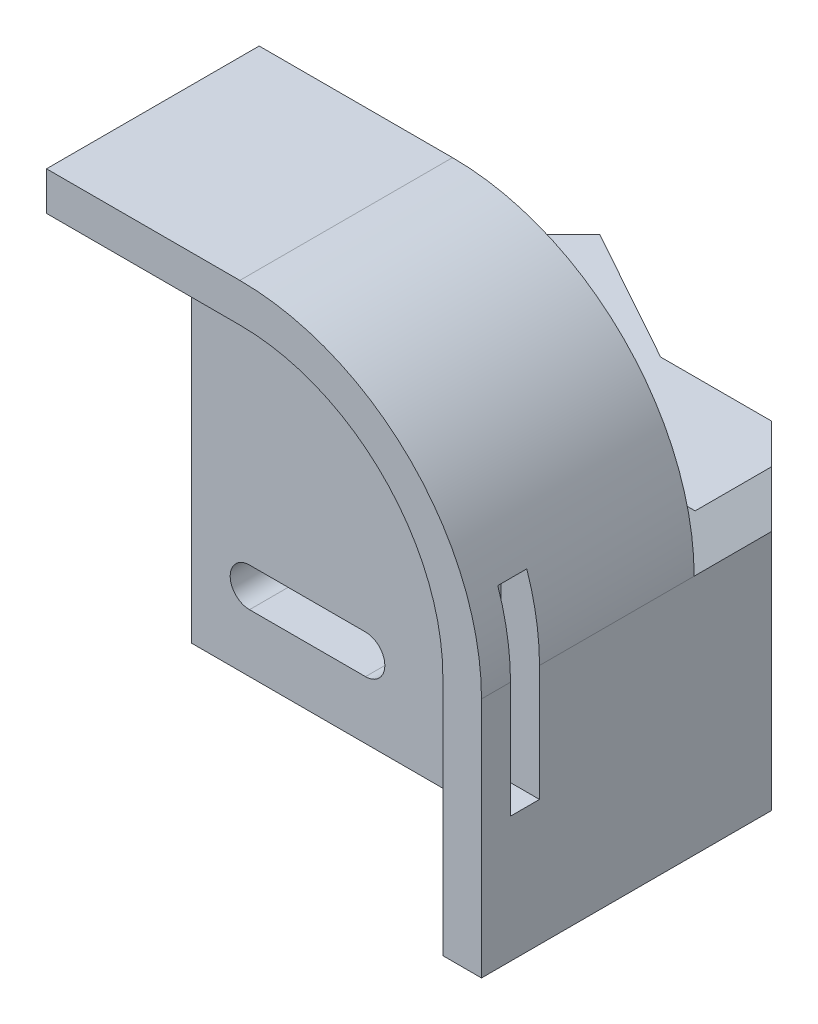
SolidWorks part; units mm, degrees
ref_plane "Front Plane" through (0, 0, 0) normal (0, 0, 1) x (1, 0, 0)
ref_plane "Top Plane" through (0, 0, 0) normal (0, 1, 0) x (1, 0, 0)
ref_plane "Right Plane" through (0, 0, 0) normal (1, 0, 0) x (0, 0, -1)
sketch "Sketch1" plane through (0, 0, 0) normal (0, 0, 1) x (1, 0, 0)
  line L0 (0, 25) -> (-20, 25)
  line L1 (-20, 25) -> (-20, -25)
  line L6 (-20, -25) -> (25, -25)
  line L7 (25, -25) -> (25, 0)
  arc A1 (25, 0) -> (0, 25) centre (0, 0) ccw
  dimension "D1" = 25
  dimension "D2" = 45
  dimension "D3" = 50
extrude "Boss-Extrude1" add sketch "Sketch1" along normal blind 7
sketch "Sketch3" plane through (0, 0, 7) normal (0, 0, 1) x (1, 0, 0)
  line L0 (25, -25) -> (25, 0) construction
  line L1 (0, 25) -> (-20, 25) construction
  line L2 (25, -25) -> (25, 0)
  line L3 (0, 25) -> (-20, 25)
  arc A0 (25, 0) -> (0, 25) centre (0, 0) ccw construction
  arc A1 (25, 0) -> (0, 25) centre (0, 0) ccw
extrude "Extrude-Thin2" add sketch "Sketch3" along normal blind 15 thin thin type one direction reverse wall 4
fillet "Fillet1" radius 7 3 edges at (-10, 21, 7) (14.8492, 14.8492, 7) (21, -12.5, 7)
sketch "Sketch5" plane through (25, 0, 0) normal (1, 0, 0) x (0, 0, -1)
  line L1 (0, -25) -> (15, -25)
  line L2 (0, -25) -> (0, 0)
  line L3 (0, 0) -> (15, 0)
  line L4 (15, -25) -> (15, 0)
  dimension "D1" = 15
extrude "Boss-Extrude2" add sketch "Sketch5" against normal blind 8
sketch "Sketch8" plane through (0, 0, 7) normal (0, 0, 1) x (1, 0, 0)
  line L0 (-20, -17) -> (-2, -17) construction
  line L1 (-20, 14) -> (-20, -25) construction
  line L2 (-20, -25) -> (14, -25) construction
  line L3 (-14, -15) -> (-2, -15)
  line L5 (-14, -19) -> (-2, -19)
  arc A0 (-2, -19) -> (-2, -15) centre (-2, -17) ccw
  arc A1 (-14, -15) -> (-14, -19) centre (-14, -17) ccw
  arc A2 (-2, -15) -> (-4, -17) centre (-2, -17) ccw construction
  arc A3 (-4, -17) -> (-2, -19) centre (-2, -17) ccw construction
  arc A4 (-12, -17) -> (-14, -15) centre (-14, -17) ccw construction
  arc A5 (-14, -19) -> (-12, -17) centre (-14, -17) ccw construction
  dimension "D1" = 4
  dimension "D2" = 12
  dimension "D3" = 6
  dimension "D4" = 8
extrude "Cut-Extrude2" cut sketch "Sketch8" against normal through all
pattern_linear "LPattern1" count 2 spacing 26 along (0, 1, 0) of "Cut-Extrude2"
chamfer "Chamfer3" distance 7 angle 45 1 edges at (25, -12.5, -15)
sketch "Sketch9" plane through (17, 0, 0) normal (-1, 0, 0) x (0, 0, 1)
  line L0 (0, 0) -> (0, -25) construction
  line L1 (-15, 0) -> (0, 0)
  line L2 (-15, 0) -> (-15, -7)
  line L3 (-15, -7) -> (0, -7)
  line L4 (0, 0) -> (0, -7)
  dimension "D1" = 7
extrude "Boss-Extrude3" add sketch "Sketch9" along normal blind 15
sketch "Sketch10" plane through (0, -7, 0) normal (0, -1, 0) x (1, 0, 0)
  line L0 (2, -15) -> (-6.9706, -15)
  line L1 (-6.9706, -15) -> (-12.6274, -9.3431)
  line L2 (-12.6274, -9.3431) -> (-16.8701, -13.5858)
  line L3 (-16.8701, -13.5858) -> (-20, -10.4558)
  line L4 (-6.9706, -7.9289) -> (-10.5061, -11.4645) construction
  line L5 (-20, -10.4558) -> (-20, 0)
  line L6 (-20, 0) -> (17, 0)
  line L7 (17, 0) -> (17, -15)
  line L8 (17, -15) -> (2, -15)
  line L9 (-4.8492, -10.0503) -> (-9.0919, -5.8076)
  line L10 (-9.0919, -5.8076) -> (-6.9706, -3.6863)
  line L11 (-6.9706, -3.6863) -> (-2.7279, -7.9289)
  line L12 (-2.7279, -7.9289) -> (-4.8492, -10.0503)
  line L14 (4.3431, -34.799) -> (-16.8701, -13.5858) construction
  dimension "D1" = 3
  dimension "D2" = 5
  dimension "D3" = 6
extrude "Boss-Extrude4" add sketch "Sketch10" against normal offset from surface 2 and the other way blind 2
sketch "Sketch13" plane through (-10.9853, 0, -10.9853) normal (-0.7071, 0, -0.7071) x (-0.7071, 0, 0.7071)
  line L0 (2.3223, -9) -> (2.3223, 2.9) construction
  line L1 (-5.6777, 2.9) -> (2.3223, 2.9)
  line L2 (-5.6777, 2.9) -> (-5.6777, 0.9)
  line L3 (-5.6777, 0.9) -> (2.3223, 0.9)
  line L4 (2.3223, 2.9) -> (2.3223, 0.9)
  line L5 (2.3223, 0.9) -> (-27.6777, 0.9) construction
  line L6 (2.3223, -9) -> (-5.6777, -9) construction
  line L7 (2.3223, -9) -> (-5.6777, -9)
  line L8 (2.3223, -9) -> (2.3223, -7)
  line L9 (2.3223, -7) -> (-5.6777, -7)
  line L10 (-5.6777, -9) -> (-5.6777, -7)
  line L11 (-5.6777, -9) -> (-5.6777, 2.9) construction
  line L12 (2.3223, -7) -> (-27.6777, -7) construction
extrude "Boss-Extrude6" add sketch "Sketch13" along normal up to surface (6 mm away) up to face at (-18.435, -3.05, -12.0208)
chamfer "Chamfer6" distance 13.5 angle 29 2 edges at (-6.9706, -8, -15) (-6.9706, 1.9, -15)
chamfer "Chamfer7" distance 3 angle 45 4 edges at (-1.5, 2.9, 0) (17, -9, -7.5) (17, -17, 0) (-1.5, -9, 0)
sketch "Sketch14" plane through (-10.9853, 0, -10.9853) normal (-0.7071, 0, -0.7071) x (-0.7071, 0, 0.7071)
  circle A0 centre (-0.6777, -3.05) radius 1.5
  dimension "D1" = 3
extrude "Cut-Extrude3" cut sketch "Sketch14" against normal blind 15
sketch "Sketch15" plane through (-15.2279, 0, -15.2279) normal (-0.7071, 0, -0.7071) x (-0.7071, 0, 0.7071)
  line L0 (2.3223, -7) -> (2.3223, 0.9) construction
  line L1 (2.6223, 1.2) -> (-12.3777, 1.2)
  line L2 (2.6223, 1.2) -> (2.6223, -7.3)
  line L3 (2.6223, -7.3) -> (-12.3777, -7.3)
  line L4 (-12.3777, 1.2) -> (-12.3777, -7.3)
  line L5 (-10.7659, -7) -> (2.3223, -7) construction
  line L6 (2.3223, 0.9) -> (-10.7659, 0.9) construction
  dimension "D1" = 0.3
  dimension "D2" = 15
  dimension "D3" = 0.3
  dimension "D4" = 0.3
extrude "Cut-Extrude4" cut sketch "Sketch15" against normal up to surface (6 mm away) up to face at (-11.5668, -3.05, -10.4038)
chamfer "Chamfer8" distance 8 angle 45 1 edges at (17, 0, -7.5)
sketch "Sketch16" plane through (21, 0, 0) normal (-1, 0, 0) x (0, 0, 1)
  line L1 (19, -12) -> (16, -12)
  line L2 (19, -12) -> (19, 8)
  line L3 (19, 8) -> (16, 8)
  line L4 (16, -12) -> (16, 8)
  point P4 (0, 0)
  point P5 (0, 0)
  point P6 (0, 0)
  point P8 (0, 0)
extrude "Cut-Extrude5" cut sketch "Sketch16" against normal through all
